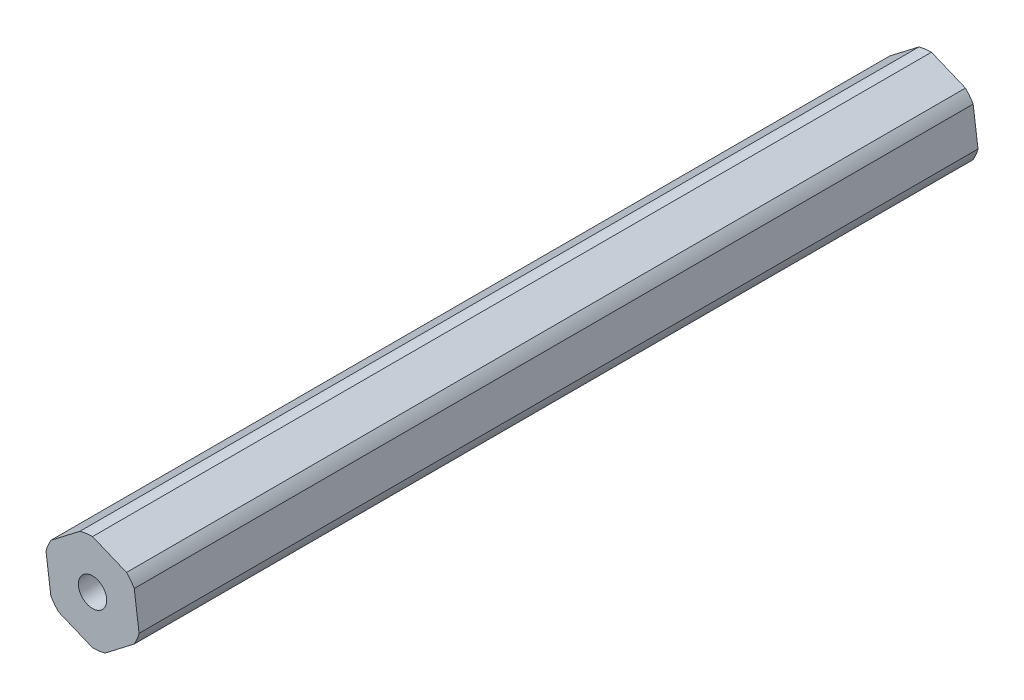
SolidWorks part; units mm, degrees
material "6061-T6 (SS)"
ref_plane "Front Plane" through (0, 0, 0) normal (0, 0, 1) x (1, 0, 0)
ref_plane "Top Plane" through (0, 0, 0) normal (0, 1, 0) x (1, 0, 0)
ref_plane "Right Plane" through (0, 0, 0) normal (1, 0, 0) x (0, 0, -1)
sketch "Sketch1" plane through (0, 0, 0) normal (0, 0, 1) x (1, 0, 0)
  line L1 (-1.7899, 6.6335) -> (-5.9502, 3.4354)
  line L2 (-6.6397, 1.7666) -> (-5.9502, -3.4353)
  line L3 (-4.8498, -4.8668) -> (0, -6.8707)
  line L4 (1.7899, -6.6335) -> (5.9502, -3.4354)
  line L5 (6.6397, -1.7666) -> (5.9502, 3.4353)
  line L6 (4.8498, 4.8668) -> (0, 6.8707)
  circle A0 centre (0, 0) radius 6.35 construction
  arc A1 (-5.9502, 3.4354) -> (-6.6397, 1.7666) centre (0, 0) ccw
  arc A2 (-5.9502, -3.4353) -> (-4.8498, -4.8668) centre (0, 0) ccw
  arc A3 (0, -6.8707) -> (1.7899, -6.6335) centre (0, 0) ccw
  arc A4 (5.9502, -3.4354) -> (6.6397, -1.7666) centre (0, 0) ccw
  arc A5 (5.9502, 3.4353) -> (4.8498, 4.8668) centre (0, 0) ccw
  arc A6 (0, 6.8707) -> (-1.7899, 6.6335) centre (0, 0) ccw
  dimension "D1" = 12.7
  dimension "D2" = 13.7414
extrude "Boss-Extrude1" add sketch "Sketch1" along normal blind 119.6975 contours L1 A1 L2 A2 L3 A3 L4 A4 L5 A5 L6 A6
hole_wizard "#10-32 Tapped Hole2" positions "Sketch4" profile "Sketch5" tap size "#10-32" standard "ANSI Inch"
sketch "Sketch4" plane through (0, 0, 119.6975) normal (0, 0, 1) x (1, 0, 0)
  point P0 (0, 0)
sketch "Sketch5" plane through (0, 0, 119.6975) normal (1, 0, 0) x (0, -1, 0)
  line L0 (0, 0) -> (0, 14.8277)
  line L1 (0, 14.8277) -> (2.0193, 13.6144)
  line L2 (2.0193, 13.6144) -> (2.0193, 0)
  line L5 (2.0193, 0) -> (0, 0)
  line L10 (0, 14.8277) -> (-2.0193, 13.6144) construction
  line L11 (0, -6.35) -> (0, 107.95) construction
  dimension "Tap Drill Dia." = 4.0386
  dimension "Tap Drill Depth" = 13.6144
  dimension "Drill Angle" = 118
cosmetic thread "Hole Thread3" parameters "D1"=9.652, "D2"=4.826
sketch "Sketch8" plane through (0, 0, 0) normal (0, 0, -1) x (-1, 0, 0)
  point P0 (0, 0)
hole_wizard "#10-32 Tapped Hole4" positions "Sketch11" profile "Sketch12" tap size "#10-32" standard "ANSI Inch"
sketch "Sketch11" plane through (0, 0, 0) normal (0, 0, -1) x (-1, 0, 0)
  point P0 (0, 0)
sketch "Sketch12" plane through (0, 0, 0) normal (1, 0, 0) x (0, 1, 0)
  line L0 (0, 0) -> (0, 16.3009)
  line L1 (0, 16.3009) -> (2.0193, 15.0876)
  line L2 (2.0193, 15.0876) -> (2.0193, 0)
  line L5 (2.0193, 0) -> (0, 0)
  line L10 (0, 16.3009) -> (-2.0193, 15.0876) construction
  line L11 (0, -6.35) -> (0, 107.95) construction
  dimension "Tap Drill Dia." = 4.0386
  dimension "Tap Drill Depth" = 15.0876
  dimension "Drill Angle" = 118
cosmetic thread "Hole Thread5" parameters "D1"=12.7, "D2"=4.826
